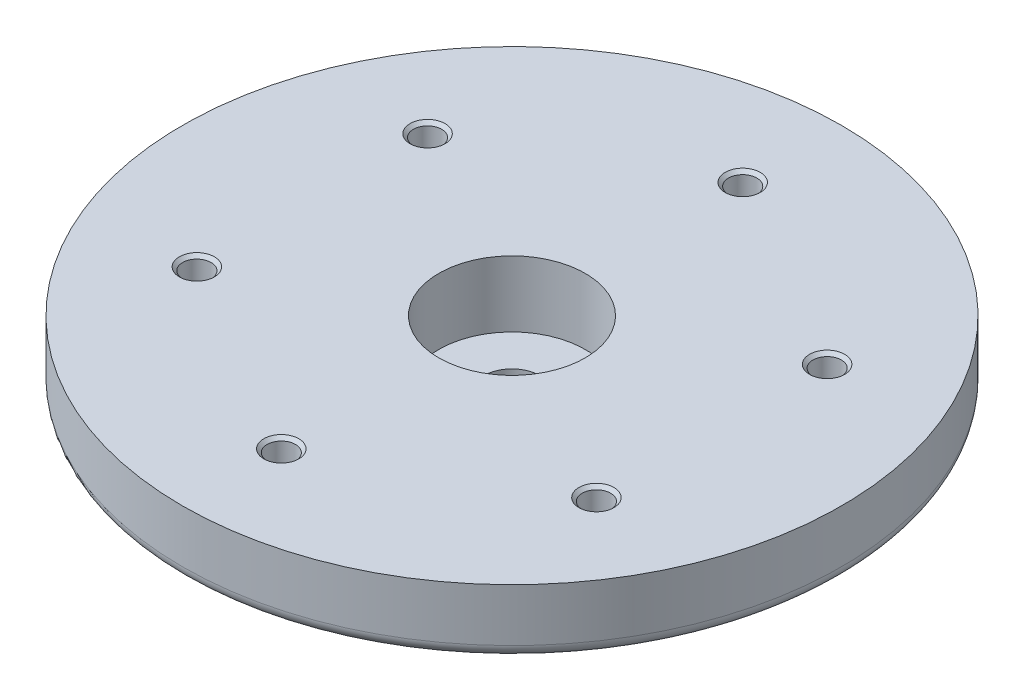
SolidWorks part; units mm, degrees
note: The reader was unsure of these and kept them because the rebuilt part matched: shared geometry of "Sketch1<3>".
ref_plane "Front Plane" through (0, 0, 0) normal (0, 0, 1) x (1, 0, 0)
ref_plane "Top Plane" through (0, 0, 0) normal (0, 1, 0) x (1, 0, 0)
ref_plane "Right Plane" through (0, 0, 0) normal (1, 0, 0) x (0, 0, -1)
sketch "Sketch1" plane through (0, 0, 0) normal (0, 1, 0) x (1, 0, 0)
  line L0 (0, 0) -> (0, 15.1055) construction
  line L1 (0, 17) -> (-0.75, 17)
  line L2 (0, 17) -> (0.75, 17)
  circle A0 centre (0, 0) radius 12.5
  circle A1 centre (0, 0) radius 17 construction
  arc A2 (-0.75, 17) -> (-1.5, 12.4097) centre (4.3336, 13.813) ccw
  arc A3 (0.75, 17) -> (1.5, 12.4097) centre (-4.3336, 13.813) cw
  dimension "D1" = 25
  dimension "D2" = 34
  dimension "D4" = 6
  dimension "D3" = 0.75
  dimension "D5" = 1.5
extrude "Boss-Extrude1" add sketch "Sketch1" along normal blind 10 contours A0
extrude "Boss-Extrude2" add sketch "Sketch1<3>" along normal blind 10 contours A3 L2 L1 A2 A0
sketch "Sketch1<3>" plane through (0, 0, 0) normal (0, 1, 0) x (1, 0, 0) same geometry as "Sketch1"
pattern_circular "CirPattern1" count 15 over 360 about axis through (0, 0, 0) along (0, 1, 0) of "Boss-Extrude2"
sketch "Sketch2" plane through (0, 10, 0) normal (0, 1, 0) x (1, 0, 0)
  circle A0 centre (0, 0) radius 4.25
  dimension "D1" = 8.5
extrude "Cut-Extrude1" cut sketch "Sketch2" against normal blind 10
fillet "Fillet1" radius 0.75 60 edges at (8.5077, 5, 9.158) (9.9971, 5, 7.5039) (14.3474, 5, 9.1495) (15.0974, 5, 7.8505) (11.4971, 5, 4.9058) (12.1849, 5, 2.7889) (16.8285, 5, 2.5229) (16.9853, 5, 1.0311) (12.4985, 5, -0.1946) (12.2658, 5, -2.4082) (16.3997, 5, -4.54) (15.9362, 5, -5.9666) (11.3388, 5, -5.2614) (10.2259, 5, -7.189) (13.1353, 5, -10.8179) (12.1316, 5, -11.9326) (8.2185, 5, -9.4184) (6.4178, 5, -10.7267) (7.5997, 5, -15.2252) (6.2294, 5, -15.8353) (3.6772, 5, -11.9469) (-3.6772, 5, -11.9469) (-6.2294, 5, -15.8353) (-7.5997, 5, -15.2252) (-6.4178, 5, -10.7267) (-8.2185, 5, -9.4184) (-12.1316, 5, -11.9326) (-13.1353, 5, -10.8179) (-10.2259, 5, -7.189) (-11.3388, 5, -5.2614) (-15.9362, 5, -5.9666) (-16.3997, 5, -4.54) (-12.2658, 5, -2.4082) (-12.4985, 5, -0.1946) (-16.9853, 5, 1.0311) (-16.8285, 5, 2.5229) (-12.1849, 5, 2.7889) (-11.4971, 5, 4.9058) (-15.0974, 5, 7.8505) (-14.3474, 5, 9.1495) (-9.9971, 5, 7.5039) (-8.5077, 5, 9.158) (-10.5991, 5, 13.3124) (-9.3856, 5, 14.1941) (-6.0807, 5, 10.9213) (1.5, 5, -12.4097) (-4.0473, 5, 11.8266) (-4.2681, 5, 16.4726) (-2.8009, 5, 16.7844) (-1.1129, 5, 12.4504) (0.75, 5, -17) (1.1129, 5, 12.4504) (-0.75, 5, -17) (2.8009, 5, 16.7844) (4.2681, 5, 16.4726) (4.0473, 5, 11.8266) (-1.5, 5, -12.4097) (6.0807, 5, 10.9213) (9.3856, 5, 14.1941) (10.5991, 5, 13.3124)
sketch "Sketch3" plane through (0, 10, 0) normal (0, 1, 0) x (1, 0, 0)
  line L0 (0, 0) -> (0, 35) construction
  line L3 (-9.6215, 5.555) -> (0, 0) construction
  circle A0 centre (0, 0) radius 11.11
  circle A1 centre (0, 0) radius 50
  circle A2 centre (0, 35) radius 2.155
  circle A3 centre (30.3109, 17.5) radius 2.155
  circle A4 centre (30.3109, -17.5) radius 2.155
  circle A5 centre (0, -35) radius 2.155
  circle A6 centre (-30.3109, -17.5) radius 2.155
  circle A7 centre (-30.3109, 17.5) radius 2.155
  point P17 (-6.691, 5.3129)
  point P19 (0, 0)
  point P40 (-6.691, 5.3129)
  dimension "D1" = 100
  dimension "D3" = 4.31
  dimension "D2" = 35
  dimension "D4" = 6
extrude "Boss-Extrude3" add sketch "Sketch3" along normal blind 10
chamfer "Chamfer1" distance 0.5 angle 45 6 edges at (-30.3109, 20, -15.345) (-30.3109, 20, 19.655) (0, 20, 37.155) (30.3109, 20, 19.655) (30.3109, 20, -15.345) (0, 20, -32.845)
fillet "Fillet2" radius 2 1 edges at (0, 10, 50)
